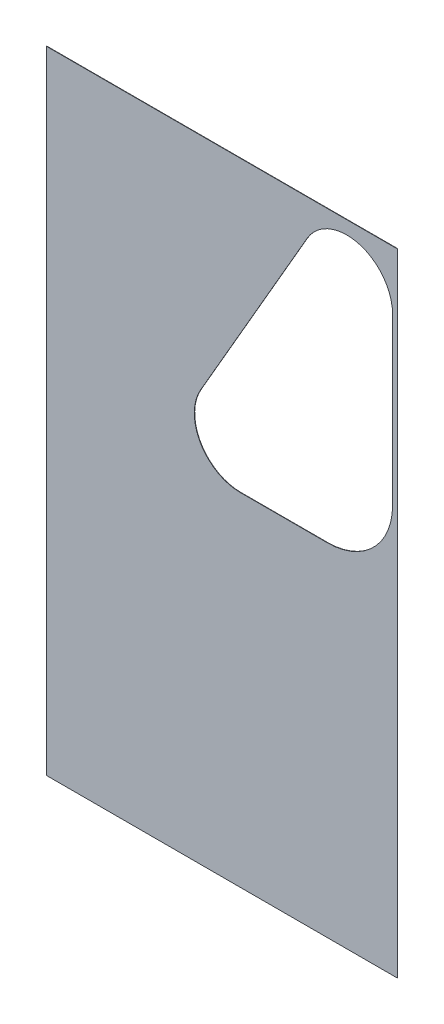
SolidWorks part; units mm, degrees
ref_plane "Front Plane" through (0, 0, 0) normal (0, 0, 1) x (1, 0, 0)
ref_plane "Top Plane" through (0, 0, 0) normal (0, 1, 0) x (1, 0, 0)
ref_plane "Right Plane" through (0, 0, 0) normal (1, 0, 0) x (0, 0, -1)
sketch "Sketch1" plane through (0, 0, 0) normal (0, 0, 1) x (1, 0, 0)
  line L1 (0, 0) -> (903, 0)
  line L2 (0, 0) -> (0, 1625)
  line L3 (0, 1625) -> (903, 1625)
  line L4 (903, 0) -> (903, 1625)
  dimension "D1" = 903
  dimension "D2" = 1625
extrude "Boss-Extrude1" add sketch "Sketch1" along normal blind 1
extrude "Cut-Extrude1" cut sketch "Sketch2" against normal through all
sketch "Sketch2" plane through (-119.4366, -43.0714, 1) normal (0, 0, 1) x (1, 0, 0)
  line L0 (1010.4366, 1516.0714) -> (1010.4366, 1091.0714)
  line L1 (842.4366, 923.0714) -> (618.1953, 923.0714)
  line L2 (516.0043, 1100.0714) -> (790.2456, 1575.0714)
  arc A0 (1010.4366, 1091.0714) -> (842.4366, 923.0714) centre (842.4366, 1091.0714) cw
  arc A1 (618.1953, 923.0714) -> (516.0043, 1100.0714) centre (618.1953, 1041.0714) cw
  arc A2 (1010.4366, 1516.0714) -> (790.2456, 1575.0714) centre (892.4366, 1516.0714) ccw
  point P5 (799.5237, 866.5543)
  point P6 (321.2838, 682.0482)
  point P7 (955.4941, 1600.8385)
  point P12 (750.0994, 693.895)
